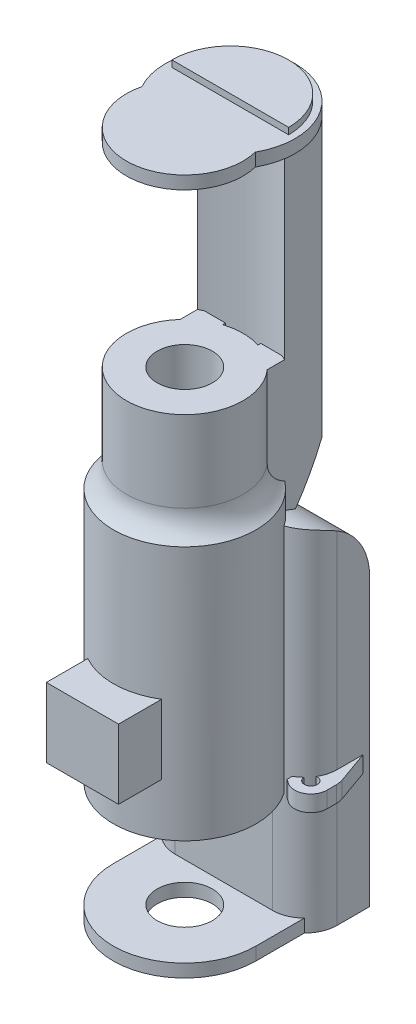
SolidWorks part; units mm, degrees
ref_plane "Front Plane" through (0, 0, 0) normal (0, 0, 1) x (1, 0, 0)
ref_plane "Top Plane" through (0, 0, 0) normal (0, 1, 0) x (1, 0, 0)
ref_plane "Right Plane" through (0, 0, 0) normal (1, 0, 0) x (0, 0, -1)
sketch "Sketch2" plane through (0, 0, 0) normal (0, 1, 0) x (1, 0, 0)
  line L0 (0, 12.9902) -> (0.0006, -12.9918) construction
  arc A0 (-8.7412, -1.8669) -> (8.7412, -1.8669) centre (0, -4.0082) ccw
  arc A1 (-8.7412, -1.8669) -> (8.7412, -1.8669) centre (0, 3.002) cw
extrude "Boss-Extrude1" add sketch "Sketch2" along normal blind 2
sketch "Sketch3" plane through (0, 2, 0) normal (0, 1, 0) x (1, 0, 0)
  line L0 (-9.0057, 3.002) -> (9.0057, 3.002)
  arc A6 (7.6664, -1.7234) -> (-7.6664, -1.7234) centre (0, 3.002) ccw
  arc A7 (-7.6664, -1.7234) -> (7.6664, -1.7234) centre (0, -4.0082) ccw
  arc A8 (9.0057, 3.002) -> (-9.0057, 3.002) centre (0, 3.002) ccw
  dimension "D1" = 1
extrude "Boss-Extrude2" add sketch "Sketch3" along normal blind 1
sketch "Sketch6" plane through (0, 0, 0) normal (0, -1, 0) x (1, 0, 0)
  line L0 (0, -13.0078) -> (0, -7.8404) construction
  line L1 (-6.7103, -10.4241) -> (6.7103, -10.4241) construction
  line L2 (-6.7103, -10.4241) -> (-6.7103, -4.6619)
  line L4 (6.7103, -4.6619) -> (6.7103, -10.4241)
  arc A0 (-8.7412, 1.8669) -> (8.7412, 1.8669) centre (0, -3.002) ccw construction
  arc A1 (-6.7103, -10.4241) -> (6.7103, -10.4241) centre (0, -3.1488) ccw
  arc A2 (-6.7103, -4.6619) -> (6.7103, -4.6619) centre (0, 8.915) ccw
  point P10 (0, -7.8404)
  point P11 (0, -10.4241)
extrude "Boss-Extrude3" add sketch "Sketch6" along normal blind 33
sketch "Sketch38" plane through (0, 0, 0) normal (1, 0, 0) x (0, 0, -1)
  line L0 (4.6619, -33) -> (4.6619, -53)
  line L1 (4.6619, -33) -> (13.0462, -33)
  arc A0 (13.0462, -33) -> (4.6619, -53) centre (-25.4769, -28.6081) cw
extrude "Boss-Extrude4" add sketch "Sketch38" along normal blind 7 and the other way blind 7
sketch "Sketch43" plane through (0, -33, 0) normal (0, 1, 0) x (1, 0, 0)
  line L0 (-6.7103, 4.6619) -> (6.7103, 4.6619)
  arc A0 (-6.7103, 4.6619) -> (6.7103, 4.6619) centre (0, -8.915) cw
extrude "Cut-Extrude2" cut sketch "Sketch43" against normal blind 21
sketch "Sketch44" plane through (0, -33, 0) normal (0, 1, 0) x (1, 0, 0)
  line L0 (0, 13.0462) -> (7, 13.0462)
  line L1 (7, 13.0462) -> (7, 4.6619)
  line L2 (7, 4.6619) -> (6.7103, 4.6619)
  line L3 (6.7103, 4.6619) -> (6.7103, 10.4241)
  arc A0 (6.7103, 10.4241) -> (0, 13.0462) centre (0, 3.1488) ccw
extrude "Cut-Extrude3" cut sketch "Sketch44" against normal blind 21
sketch "Sketch45" plane through (0, -33, 0) normal (0, 1, 0) x (1, 0, 0)
  line L0 (-6.7103, 4.6619) -> (-7, 4.6619)
  line L1 (-7, 4.6619) -> (-7, 13.0462)
  line L2 (-7, 13.0462) -> (0, 13.0462)
  line L3 (-6.7103, 10.4241) -> (-6.7103, 4.6619)
  arc A0 (6.7103, 10.4241) -> (-6.7103, 10.4241) centre (0, 3.1488) ccw construction
  arc A1 (0, 13.0462) -> (-6.7103, 10.4241) centre (0, 3.1488) ccw
extrude "Cut-Extrude4" cut sketch "Sketch45" against normal blind 21
sketch "Sketch46" plane through (0, 0, 0) normal (0, -1, 0) x (1, 0, 0)
  line L0 (-8.9996, 4.0082) -> (8.9996, 4.0082) construction
  circle A0 centre (0, 4.0082) radius 4.25
  arc A1 (8.7412, 1.8669) -> (-8.7412, 1.8669) centre (0, 4.0082) ccw construction
extrude "Cut-Extrude5" cut sketch "Sketch46" against normal blind 1
ref_plane "Plane1" through (0, -30, 0) normal (0, 1, 0) x (1, 0, 0)
sketch "Sketch47" plane through (0, -30, 0) normal (0, 1, 0) x (1, 0, 0)
  line L0 (-8.9996, -4.0082) -> (8.9996, -4.0082) construction
  arc A0 (-8.7412, -1.8669) -> (8.7412, -1.8669) centre (0, -4.0082) ccw construction
  circle A1 centre (0, -4.0082) radius 9
extrude "Boss-Extrude5" add sketch "Sketch47" against normal blind 17 separate body
ref_plane "Plane2" through (0, -47, 0) normal (0, 1, 0) x (1, 0, 0)
sketch "Sketch50" plane through (0, -47, 0) normal (0, 1, 0) x (1, 0, 0)
  line L0 (-8.9996, -4.0082) -> (8.9996, -4.0082) construction
  arc A0 (-8.7412, -1.8669) -> (8.7412, -1.8669) centre (0, -4.0082) ccw construction
  circle A1 centre (0, -4.0082) radius 11
extrude "Boss-Extrude6" add sketch "Sketch50" against normal blind 38.5
fillet "Fillet7" radius 4.5 1 edges at (0, -47, 13.0082)
ref_plane "Plane3" through (0, 0, -5) normal (0, 0, 1) x (1, 0, 0)
sketch "Sketch52" plane through (0, 0, -5) normal (0, 0, 1) x (1, 0, 0)
  line L0 (12.1, -30) -> (-12.1, -30) construction
  line L1 (-6.7103, -30) -> (-2.7103, -30)
  line L2 (-6.7103, -30) -> (-6.7103, -47)
  line L3 (-6.7103, -47) -> (-2.7103, -47)
  line L4 (-2.7103, -30) -> (-2.7103, -47)
  line L5 (-6.7103, -30) -> (-2.7103, -47) construction
  line L6 (-6.7103, -47) -> (-2.7103, -30) construction
  line L7 (-6.7103, -46.217) -> (-6.7103, 0) construction
  line L8 (12.1, -47) -> (-12.1, -47) construction
  line L9 (6.7103, -46.217) -> (6.7103, 0) construction
  line L10 (6.7103, -30) -> (2.7103, -30)
  line L11 (6.7103, -30) -> (6.7103, -47)
  line L12 (6.7103, -47) -> (2.7103, -47)
  line L13 (2.7103, -30) -> (2.7103, -47)
  line L14 (6.7103, -30) -> (2.7103, -47) construction
  line L15 (6.7103, -47) -> (2.7103, -30) construction
  point P4 (-4.7103, -38.5)
  point P15 (4.7103, -38.5)
  dimension "D1" = 4
  dimension "D2" = 4
extrude "Boss-Extrude7" add sketch "Sketch52" along normal blind 4.5
sketch "Sketch54" plane through (0, 0, -5) normal (0, 0, 1) x (1, 0, 0)
  line L0 (12.5, -49.8) -> (-12.5, -49.8) construction
  line L2 (12.5, -49.8) -> (-12.5, -49.8)
  line L3 (12.5, -49.8) -> (12.5, -103.8)
  line L4 (12.5, -103.8) -> (-12.5, -103.8)
  line L5 (-12.5, -49.8) -> (-12.5, -103.8)
  line L6 (12.5, -49.8) -> (-12.5, -103.8) construction
  line L7 (12.5, -103.8) -> (-12.5, -49.8) construction
  spline S1 degree 3 poles (-6.7103, -52.9429) (-6.2868, -52.5385) (-5.8353, -52.1509) (-5.1057, -51.6065) (-4.8537, -51.4313) (-4.3291, -51.0967) (-4.055, -50.9365) (-3.2088, -50.4935) (-2.6136, -50.2468) (-1.6563, -49.9838) (-1.3295, -49.9155) (-0.6727, -49.824) (-0.3409, -49.8002) (0.3301, -49.7997) (0.6674, -49.8235) (1.325, -49.9147) (1.6482, -49.982) (2.2847, -50.156) (2.5976, -50.2629) (3.1971, -50.5041) (3.4863, -50.6389) (4.3269, -51.0783) (4.8551, -51.4198) (5.8337, -52.1494) (6.2865, -52.5382) (6.7103, -52.9429) knots 0 0 0 0 0.125 0.125 0.1875 0.1875 0.25 0.25 0.375 0.375 0.4375 0.4375 0.5 0.5 0.5625 0.5625 0.625 0.625 0.6875 0.6875 0.75 0.75 0.875 0.875 1 1 1 1 construction
  point P3 (0, -49.8)
  point P7 (0, -76.8)
  dimension "D1" = 54
extrude "Boss-Extrude8" add sketch "Sketch54" against normal blind 7 and the other way blind 3
fillet "Fillet11" radius 10 1 edges at (0, -49.8, -12)
fillet "Fillet16" radius 5 2 edges at (12.5, -76.8, -2) (-12.5, -76.8, -2)
sketch "Sketch55" plane through (0, -103.8, 0) normal (0, -1, 0) x (1, 0, 0)
  line L0 (-11, -5) -> (11, -5)
  line L4 (-11, 4.0082) -> (-11, -5)
  line L5 (13.75, -5) -> (-13.75, -5) construction
  line L6 (11, 4.0082) -> (11, -5)
  arc A0 (-11, 4.0082) -> (11, 4.0082) centre (0, 4.0335) cw
  arc A1 (9.0491, -2.246) -> (-9.0491, -2.246) centre (0, 4.0082) ccw construction
extrude "Boss-Extrude9" add sketch "Sketch55" against normal blind 2
sketch "Sketch56" plane through (0, -30, 0) normal (0, 1, 0) x (1, 0, 0)
  line L0 (-9, -4.0082) -> (9, -4.0082) construction
  arc A0 (-6.7103, 1.9895) -> (6.7103, 1.9895) centre (0, -4.0082) ccw construction
  arc A1 (-6.7103, 1.9895) -> (6.7103, 1.9895) centre (0, -4.0082) ccw construction
  circle A2 centre (0, -4.0082) radius 4.25
extrude "Cut-Extrude6" cut sketch "Sketch56" against normal blind 83
ref_plane "Plane4" through (0, -85.5, 0) normal (0, 1, 0) x (1, 0, 0)
sketch "Sketch58" plane through (0, -85.5, 0) normal (0, 1, 0) x (1, 0, 0)
  line L0 (-12.5038, 10.9676) -> (-14.2844, 5.9548)
  line L1 (-14.4574, 4.9506) -> (-14.4574, 3.4675)
  line L2 (-9.935, 1.8145) -> (-9.935, 2.633)
  line L3 (-9.935, 2.633) -> (-11.0584, 3.4724)
  line L4 (-11.0584, 3.4724) -> (-11.5033, 4.0043)
  line L5 (-11.5033, 4.0043) -> (-11.7583, 4.3796)
  line L6 (-11.7583, 4.3796) -> (-11.8857, 4.6267)
  line L7 (-11.8857, 4.6267) -> (-12.1416, 5.1232)
  line L8 (-12.1416, 5.1232) -> (-12.2291, 5.3726)
  line L9 (-12.2291, 5.3726) -> (-12.2975, 5.567)
  line L10 (-12.2975, 5.567) -> (-12.4084, 6.0925)
  line L11 (-12.4084, 6.0925) -> (-12.4393, 6.239)
  line L12 (-12.4393, 6.239) -> (-12.5038, 6.9676)
  line L13 (-12.5038, 6.9676) -> (-12.5038, 8.8993)
  line L14 (-12.5038, 8.8993) -> (-12.5038, 9.6163)
  line L15 (-12.5038, 9.6163) -> (-12.5038, 10.7055)
  line L18 (0, -15.4438) -> (0, 15.4438) construction
  line L19 (12.5038, 10.9676) -> (14.2844, 5.9548)
  line L22 (12.5038, 9.6163) -> (12.5038, 10.7055)
  line L23 (12.5038, 8.8993) -> (12.5038, 9.6163)
  line L24 (12.5038, 6.9676) -> (12.5038, 8.8993)
  line L25 (12.4393, 6.239) -> (12.5038, 6.9676)
  line L26 (12.4084, 6.0925) -> (12.4393, 6.239)
  line L27 (12.2975, 5.567) -> (12.4084, 6.0925)
  line L28 (12.2291, 5.3726) -> (12.2975, 5.567)
  line L29 (12.1416, 5.1232) -> (12.2291, 5.3726)
  line L30 (11.8857, 4.6267) -> (12.1416, 5.1232)
  line L31 (11.7583, 4.3796) -> (11.8857, 4.6267)
  line L32 (11.5033, 4.0043) -> (11.7583, 4.3796)
  line L33 (11.0584, 3.4724) -> (11.5033, 4.0043)
  line L34 (9.935, 2.633) -> (11.0584, 3.4724)
  line L35 (9.935, 1.8145) -> (9.935, 2.633)
  line L36 (14.4574, 4.9506) -> (14.4574, 3.4675)
  line L37 (-12.5038, 10.9676) -> (-12.5038, 10.7055)
  line L38 (12.5038, 10.9676) -> (12.5038, 10.7055)
  arc A0 (-14.2844, 5.9548) -> (-14.4574, 4.9506) centre (-10.0366, 4.7058) ccw
  arc A1 (-14.4574, 3.4675) -> (-10.404, 1.509) centre (-11.9575, 3.4675) ccw
  arc A2 (-10.404, 1.509) -> (-9.935, 1.8145) centre (-8.5343, -0.8481) cw
  circle A3 centre (-11.9575, 3.4675) radius 1
  circle A4 centre (11.9575, 3.4675) radius 1
  arc A5 (10.404, 1.509) -> (9.935, 1.8145) centre (8.5343, -0.8481) ccw
  arc A6 (14.4574, 3.4675) -> (10.404, 1.509) centre (11.9575, 3.4675) cw
  arc A7 (14.2844, 5.9548) -> (14.4574, 4.9506) centre (10.0366, 4.7058) cw
  arc A8 (-12.5, 7) -> (-9.0491, 2.246) centre (-7.5, 7) ccw construction
  arc A9 (8.7412, -1.8669) -> (-8.7412, -1.8669) centre (0, 3.002) ccw construction
  arc A10 (-11, 3.4293) -> (-7.5, 2) centre (-7.5, 7) ccw construction
extrude "Boss-Extrude10" add sketch "Sketch58" along normal blind 2.5 contours A3 L6 L7 L8 L9 L10 L11 L12 L13 L14 L15 L37 L0 A0 L1 A1 A2 L2 L3 | A7 L19 L38 L22 L23 L24 L25 L26 L27 L28 L29 L30 L31 A4 L34 L35 A5 A6 L36 region at (-12.7906, -85.5, -4.4102) region at (12.7906, -85.5, -4.4102)
sketch "Sketch59" plane through (0, 0, -12) normal (0, 0, -1) x (-1, 0, 0)
  line L1 (-7.5, -79.9283) -> (7.5, -79.9283)
  line L2 (-7.5, -79.9283) -> (-7.5, -64.9283)
  line L3 (-7.5, -64.9283) -> (7.5, -64.9283)
  line L4 (7.5, -79.9283) -> (7.5, -64.9283)
  line L5 (-7.5, -79.9283) -> (7.5, -64.9283) construction
  line L6 (-7.5, -64.9283) -> (7.5, -79.9283) construction
  point P0 (0, -72.4283)
  dimension "D1" = 15
  dimension "D2" = 15
extrude "Cut-Extrude7" cut sketch "Sketch59" against normal blind 2.5
ref_plane "Plane5" through (0, 0, 15) normal (0, 0, 1) x (1, 0, 0)
sketch "Sketch60" plane through (0, 0, 15) normal (0, 0, 1) x (1, 0, 0)
  line L0 (-5.3527, -66.792) -> (5.7803, -66.792)
  line L1 (-5.3527, -66.792) -> (-5.3527, -77.5081)
  line L2 (-5.3527, -77.5081) -> (5.7803, -77.5081)
  line L3 (5.7803, -66.792) -> (5.7803, -77.5081)
  line L4 (-5.3527, -66.792) -> (5.7803, -77.5081) construction
  line L5 (-5.3527, -77.5081) -> (5.7803, -66.792) construction
  point P4 (0.2138, -72.1501)
extrude "Boss-Extrude11" add sketch "Sketch60" along normal blind 5 and the other way blind 5
